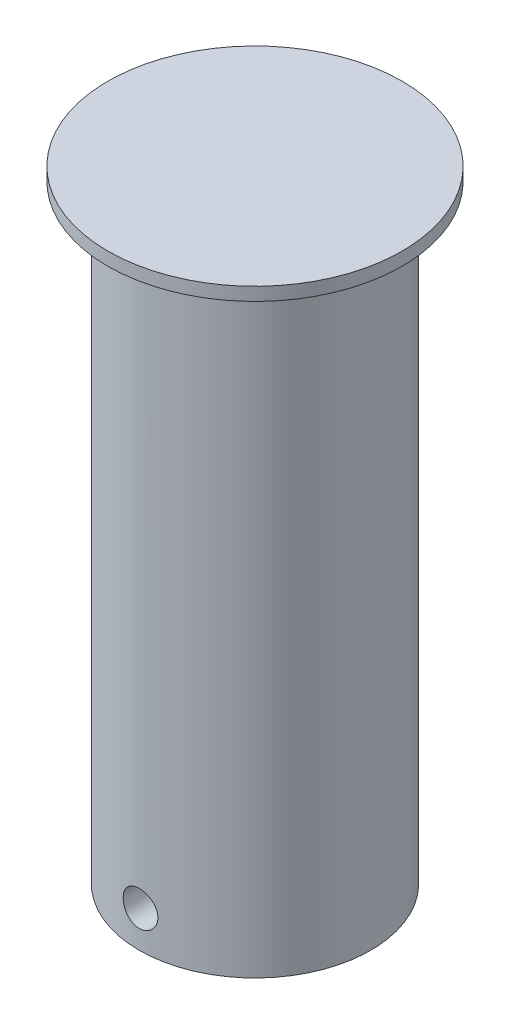
SolidWorks part; units mm, degrees
ref_plane "Front Plane" through (0, 0, 0) normal (0, 0, 1) x (1, 0, 0)
ref_plane "Top Plane" through (0, 0, 0) normal (0, 1, 0) x (1, 0, 0)
ref_plane "Right Plane" through (0, 0, 0) normal (1, 0, 0) x (0, 0, -1)
sketch "Sketch1" plane through (0, 0, 0) normal (0, 1, 0) x (1, 0, 0)
  circle A0 centre (0, 0) radius 15
  dimension "D1" = 30
extrude "Boss-Extrude1" add sketch "Sketch1" along normal blind 27
sketch "Sketch2" plane through (0, 0, 0) normal (0, -1, 0) x (1, 0, 0)
  circle A0 centre (0, 0) radius 15
  circle A1 centre (0, 0) radius 15 construction
extrude "Boss-Extrude2" add sketch "Sketch2" along normal blind 1.7
sketch "Sketch3" plane through (0, -1.7, 0) normal (0, -1, 0) x (1, 0, 0)
  line L1 (-2.8001, 4.85) -> (-5.6003, 0)
  line L2 (-5.6003, 0) -> (-2.8001, -4.85)
  line L3 (-2.8001, -4.85) -> (2.8001, -4.85)
  line L4 (2.8001, -4.85) -> (5.6003, 0)
  line L5 (5.6003, 0) -> (2.8001, 4.85)
  line L6 (2.8001, 4.85) -> (-2.8001, 4.85)
  circle A0 centre (0, 0) radius 4.85 construction
  dimension "D1" = 9.7
extrude "Cut-Extrude1" cut sketch "Sketch3" against normal blind 23.4
sketch "Sketch5" plane through (0, 27, 0) normal (0, 1, 0) x (1, 0, 0)
  circle A4 centre (0, 0) radius 15
extrude "Boss-Extrude3" add sketch "Sketch5" along normal blind 51.8
sketch "Sketch6" plane through (0, 0, 0) normal (0, 0, 1) x (1, 0, 0)
  line L0 (0, 0) -> (0, 27) construction
  circle A0 centre (0, 3) radius 2.2479
  dimension "D1" = 4.4958
  dimension "D2" = 24
extrude "Cut-Extrude3" cut sketch "Sketch6" against normal through all both and the other way through all
sketch "Sketch10" plane through (0, 78.8, 0) normal (0, 1, 0) x (1, 0, 0)
  circle A0 centre (0, 0) radius 19.07
  dimension "D1" = 38.14
extrude "Boss-Extrude4" add sketch "Sketch10" against normal blind 1.7
